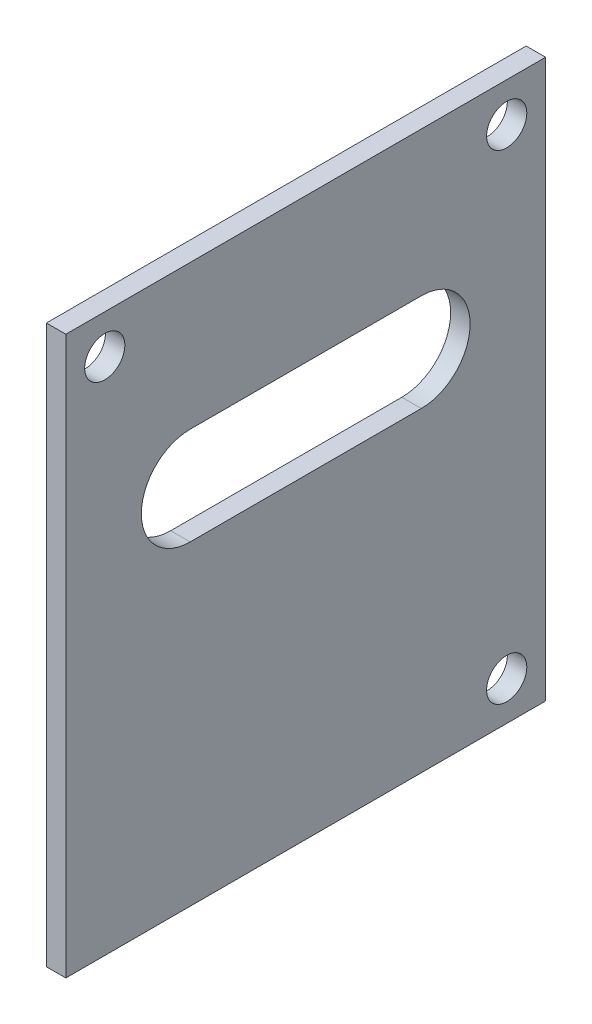
SolidWorks part; units mm, degrees
ref_plane "Front Plane" through (0, 0, 0) normal (0, 0, 1) x (1, 0, 0)
ref_plane "Top Plane" through (0, 0, 0) normal (0, 1, 0) x (1, 0, 0)
ref_plane "Right Plane" through (0, 0, 0) normal (1, 0, 0) x (0, 0, -1)
sketch "Sketch1" plane through (0, 0, 0) normal (1, 0, 0) x (0, 0, -1)
  line L0 (0, 0) -> (0, -50000) construction
  line L1 (18.5, 21.5) -> (-18.5, 21.5)
  line L2 (18.5, 21.5) -> (18.5, -21.5)
  line L3 (18.5, -21.5) -> (-18.5, -21.5)
  line L4 (-18.5, 21.5) -> (-18.5, -21.5)
  line L5 (18.5, 21.5) -> (-18.5, -21.5) construction
  line L6 (18.5, -21.5) -> (-18.5, 21.5) construction
  line L7 (-8.9136, 6.5958) -> (8.9136, 6.5958) construction
  line L8 (-8.9136, 10.359) -> (8.9136, 10.359)
  line L9 (-8.9136, 2.8325) -> (8.9136, 2.8325)
  circle A0 centre (-15.5, 18.5) radius 1.55
  circle A1 centre (15.5, 18.5) radius 1.55
  circle A2 centre (15.5, -18.5) radius 1.55
  arc A3 (-8.9136, 10.359) -> (-8.9136, 2.8325) centre (-8.9136, 6.5958) ccw
  arc A4 (8.9136, 2.8325) -> (8.9136, 10.359) centre (8.9136, 6.5958) ccw
  point P0 (0, 0)
  point P14 (0, -21.5)
  point P17 (0, 6.5958)
  point P22 (0, 8.576)
  point P23 (-8.9136, 10.359)
  dimension "D9" = 3.1
  dimension "D1" = 43
  dimension "D2" = 37
  dimension "D3" = 3
  dimension "D4" = 3
  dimension "D5" = 3
  dimension "D6" = 3
  dimension "D7" = 3
  dimension "D8" = 3
extrude "Boss-Extrude1" add sketch "Sketch1" along normal blind 1.5 contours L1 L4 L3 L2 A2 A1 A0 region at (0, -0.9485, 0.0842)
